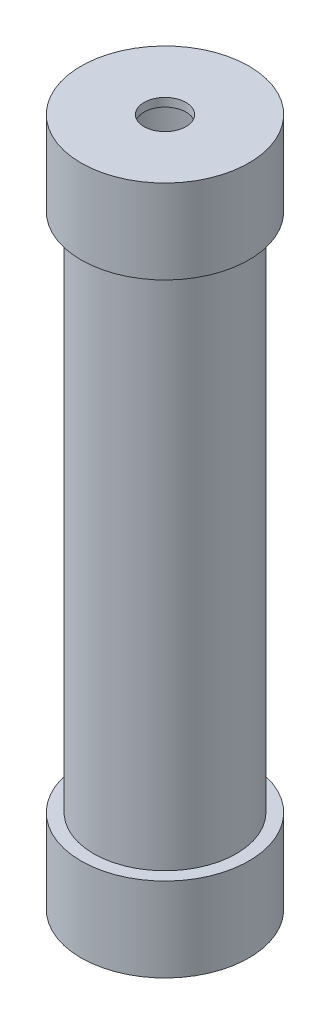
SolidWorks part; units mm, degrees
ref_plane "前视基准面" through (0, 0, 0) normal (0, 0, 1) x (1, 0, 0)
ref_plane "上视基准面" through (0, 0, 0) normal (0, 1, 0) x (1, 0, 0)
ref_plane "右视基准面" through (0, 0, 0) normal (1, 0, 0) x (0, 0, -1)
sketch "草图1" plane through (0, 0, 0) normal (0, 1, 0) x (1, 0, 0)
  line L0 (0, 20) -> (0, 15)
  line L1 (0, -15) -> (0, -20)
  arc A0 (0, -15) -> (0, 15) centre (0, 0) ccw
  arc A1 (0, -20) -> (0, 20) centre (0, 0) ccw
  dimension "D1" = 30
  dimension "D2" = 40
extrude "凸台-拉伸1" add sketch "草图1" along normal blind 20
sketch "草图2" plane through (0, 20, 0) normal (0, 1, 0) x (1, 0, 0)
  line L0 (0, 20) -> (0, 5)
  line L1 (0, -5) -> (0, -20)
  arc A0 (0, -20) -> (0, 20) centre (0, 0) ccw
  arc A1 (0, -5) -> (0, 5) centre (0, 0) ccw
  dimension "D1" = 10
extrude "凸台-拉伸2" add sketch "草图2" against normal blind 2
sketch "草图3" plane through (0, 0, 0) normal (0, 1, 0) x (1, 0, 0)
  line L0 (0, 17) -> (0, 15)
  line L1 (0, -15) -> (0, -17)
  arc A0 (0, -17) -> (0, 17) centre (0, 0) ccw
  arc A1 (0, -15) -> (0, 15) centre (0, 0) ccw
  dimension "D1" = 34
  dimension "D2" = 30
extrude "凸台-拉伸3" add sketch "草图3" against normal blind 124
sketch "草图4" plane through (0, -124, 0) normal (0, -1, 0) x (1, 0, 0)
  line L2 (0, 20) -> (0, 15)
  line L3 (0, -15) -> (0, -20)
  arc A4 (0, 20) -> (0, -20) centre (0, 0) cw
  circle A5 centre (0, 0) radius 20 construction
  arc A6 (0, 15) -> (0, -15) centre (0, 0) cw
  arc A7 (0, -15) -> (0, 15) centre (0, 0) ccw construction
extrude "凸台-拉伸4" add sketch "草图4" along normal blind 20
mirror "镜向1" of "凸台-拉伸4", "凸台-拉伸3", "凸台-拉伸2", "凸台-拉伸1"
